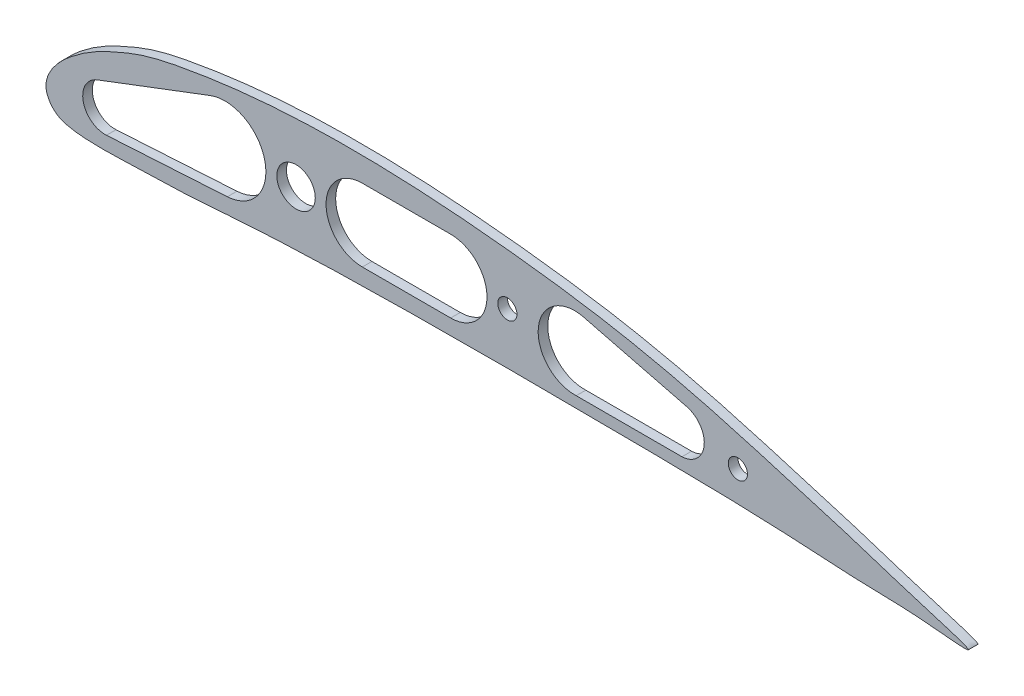
SolidWorks part; units mm, degrees
material "Teak"
ref_plane "Front Plane" through (0, 0, 0) normal (0, 0, 1) x (1, 0, 0)
ref_plane "Top Plane" through (0, 0, 0) normal (0, 1, 0) x (1, 0, 0)
ref_plane "Right Plane" through (0, 0, 0) normal (1, 0, 0) x (0, 0, -1)
curve "Curve1"
  spline degree 3 poles (23.9495, 0.1202, 0) (26.1315, -0.1443, 0) (23.9339, 0.4767, 0) (22.5552, 0.9498, 0) (20.2886, 1.6238, 0) (17.8123, 2.3508, 0) (15.2534, 2.8897, 0) (12.7077, 3.2191, 0) (10.1639, 3.4311, 0) (7.6179, 3.4769, 0) (5.494, 3.3385, 0) (3.8021, 3.0837, 0) (2.7273, 2.8627, 0) (1.8943, 2.5164, 0) (1.2423, 2.2051, 0) (0.7097, 1.8304, 0) (0.2115, 1.374, 0) (-0.1637, 0.7412, 0) (0.2368, 0.1946, 0) (0.7316, 0.0524, 0) (1.2691, 0.0185, 0) (1.9053, 0.0199, 0) (2.7513, 0.0657, 0) (3.8117, 0.0713, 0) (5.5015, 0.2215, 0) (7.6189, 0.3162, 0) (10.1596, 0.361, 0) (12.7007, 0.3733, 0) (15.2375, 0.3558, 0) (17.7899, 0.3373, 0) (20.2858, 0.2762, 0) (22.5405, 0.1142, 0) (23.9495, 0.1202, 0) (26.1315, -0.1443, 0) (23.9339, 0.4767, 0) knots -0.096906 -0.048454 -0.024239 0 0.025556 0.05096 0.101553 0.151805 0.201252 0.250083 0.298629 0.347026 0.395536 0.420003 0.444885 0.457915 0.471441 0.486208 0.494594 0.510948 0.521395 0.527824 0.539982 0.55208 0.564187 0.588394 0.612649 0.661101 0.709502 0.757894 0.806286 0.85468 0.903094 0.951546 0.975761 1 1.025556 1.05096 1.101553 periodic
sketch "Sketch1" plane through (0, 0, 0) normal (0, 0, 1) x (1, 0, 0)
  line L0 (-847.6, 21.4122) -> (49152.4, 21.4122) construction
  line L1 (0, -1000) -> (0, 49000) construction
  line L2 (0, -14.8388) -> (82.55, -14.8388) construction
  line L3 (152.4, -14.8388) -> (228.6, -14.8388) construction
  line L4 (152.4, -14.8388) -> (82.55, -14.8388) construction
  line L5 (82.55, -1014.8388) -> (82.55, 48985.1612) construction
  line L6 (152.4, -1014.8388) -> (152.4, 48985.1612) construction
  circle A0 centre (82.55, 21.4122) radius 6.35
  circle A1 centre (152.4, 21.4122) radius 3.175
  circle A2 centre (228.6, 13.7136) radius 3.175
  spline S1 degree 3 poles (287.3943, 1.4424) (313.578, -1.7317) (287.2067, 5.7201) (270.6628, 11.3971) (243.4633, 19.4859) (213.7479, 28.21) (183.0402, 34.6766) (152.4919, 38.629) (121.967, 41.1729) (91.4149, 41.723) (65.9275, 40.062) (45.625, 37.0046) (32.7277, 34.3521) (22.7318, 30.1965) (14.9072, 26.4613) (8.5163, 21.9644) (2.5375, 16.4885) (-1.9645, 8.8939) (2.8419, 2.3349) (8.7788, 0.629) (15.2288, 0.2218) (22.8636, 0.2391) (33.0156, 0.7881) (45.7404, 0.8553) (66.0184, 2.6584) (91.4266, 3.7949) (121.9153, 4.3322) (152.4083, 4.4791) (182.8498, 4.2691) (213.4792, 4.0477) (243.4301, 3.314) (270.4865, 1.3705) (287.3943, 1.4424) (313.578, -1.7317) (287.2067, 5.7201) knots -0.096906 -0.048454 -0.024239 0 0.025556 0.05096 0.101553 0.151805 0.201252 0.250083 0.298629 0.347026 0.395536 0.420003 0.444885 0.457915 0.471441 0.486208 0.494594 0.510948 0.521395 0.527824 0.539982 0.55208 0.564187 0.588394 0.612649 0.661101 0.709502 0.757894 0.806286 0.85468 0.903094 0.951546 0.975761 1 1.025556 1.05096 1.101553 only from (304.8, 0) to (304.8, 0)
  dimension "D1" = 82.55
  dimension "D4" = 12.7
  dimension "D2" = 69.85
  dimension "D3" = 76.2
extrude "Boss-Extrude1" add sketch "Sketch1" along normal blind 1.5875 and the other way blind 1.5875 contours S1 | A0 | A2 | A1
sketch "Sketch2" plane through (0, 0, 1.5875) normal (0, 0, 1) x (1, 0, 0)
  line L9 (177.5757, 31.6497) -> (211.5027, 23.1049)
  line L11 (0, 0) -> (0, -33.8113) construction
  line L14 (0, -33.8113) -> (82.55, -33.8113) construction
  line L15 (82.55, -33.8113) -> (152.4, -33.8113) construction
  line L16 (152.4, -33.8113) -> (228.6, -33.8113) construction
  line L17 (175.1649, 7.9231) -> (210.1171, 7.9231)
  line L18 (82.55, -1033.8113) -> (82.55, 48966.1887) construction
  line L19 (152.4, -1033.8113) -> (152.4, 48966.1887) construction
  line L20 (228.6, -1033.8113) -> (228.6, 48966.1887) construction
  line L21 (-917.45, 21.4122) -> (49082.55, 21.4122) construction
  line L22 (88.9, -978.5878) -> (88.9, 49021.4122) construction
  line L23 (149.225, -978.5878) -> (149.225, 49021.4122) construction
  line L24 (88.9, -15.1784) -> (149.225, -15.1784) construction
  line L25 (119.0625, -1015.1784) -> (119.0625, 48984.8216) construction
  line L28 (104.4575, 21.4122) -> (133.6675, 21.4122) construction
  line L29 (104.4575, 33.4062) -> (133.6675, 33.4062)
  line L30 (104.4575, 9.4182) -> (133.6675, 9.4182)
  line L31 (19.8733, 4.8397) -> (59.8329, 7.205)
  line L32 (16.8042, 19.1659) -> (54.2258, 33.3781)
  arc A11 (177.5757, 31.6497) -> (175.1649, 7.9231) centre (174.6323, 19.963) ccw
  arc A15 (210.1171, 7.9231) -> (211.5027, 23.1049) centre (209.808, 15.6054) ccw
  arc A17 (104.4575, 33.4062) -> (104.4575, 9.4182) centre (104.4575, 21.4122) ccw
  arc A18 (133.6675, 9.4182) -> (133.6675, 33.4062) centre (133.6675, 21.4122) ccw
  arc A19 (59.8329, 7.205) -> (54.2258, 33.3781) centre (59.0329, 20.7208) ccw
  arc A20 (16.8042, 19.1659) -> (19.8733, 4.8397) centre (19.4354, 12.2377) ccw
  circle A21 centre (82.55, 21.4122) radius 6.35
  point P25 (119.0625, 21.4122)
  point P28 (19.0457, 14.3222)
  point P47 (119.0625, -15.1784)
  dimension "D1" = 82.55
  dimension "D2" = 69.85
  dimension "D3" = 76.2
extrude "Cut-Extrude1" cut sketch "Sketch2" against normal blind 83.312 contours L31 A19 L32 A20 | L29 A18 L30 A17 | L9 A11 L17 A15
